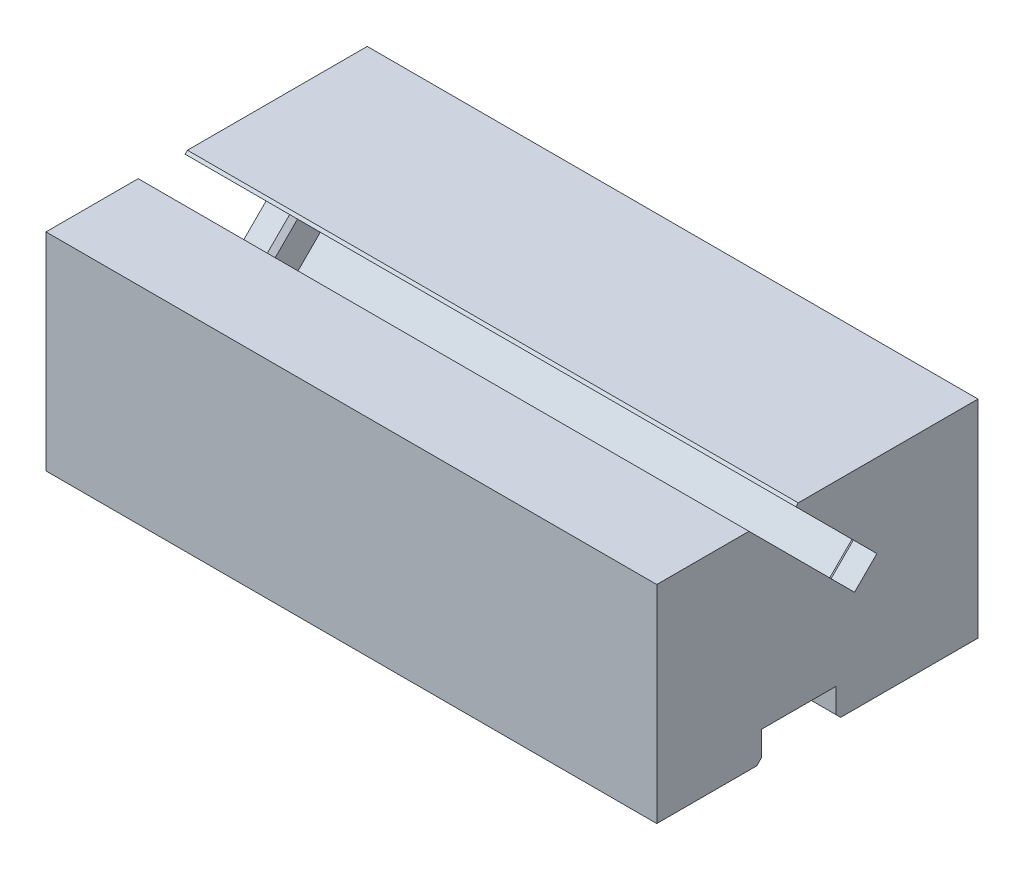
SolidWorks part; units mm, degrees
ref_plane "Front Plane" through (0, 0, 0) normal (0, 0, 1) x (1, 0, 0)
ref_plane "Top Plane" through (0, 0, 0) normal (0, 1, 0) x (1, 0, 0)
ref_plane "Right Plane" through (0, 0, 0) normal (1, 0, 0) x (0, 0, -1)
sketch "Sketch1" plane through (0, 0, 0) normal (1, 0, 0) x (0, 0, -1)
  line L0 (0, 0) -> (0, 19.2836)
  line L1 (0, 19.2836) -> (10, 19.2836)
  line L2 (34.8437, 19.2836) -> (34.8437, 0)
  line L3 (34.8437, 0) -> (0, 0)
  line L4 (10, 19.2836) -> (24.2836, 5)
  line L5 (24.2836, 5) -> (26.7054, 7.4218)
  line L6 (26.7054, 7.4218) -> (14.8437, 19.2836)
  line L7 (23.877, 10.2503) -> (21.4551, 7.8284)
  line L8 (14.8437, 19.2836) -> (34.8437, 19.2836)
  dimension "D2" = 20.2
  dimension "D3" = 3.425
  dimension "D4" = 10
  dimension "D5" = 20
  dimension "D6" = 5
  dimension "D7" = 4
  dimension "D1" = 45
extrude "Boss-Extrude1" add sketch "Sketch1" along normal blind 66.25 contours L8 L6 L5 L4 L1 L0 L3 L2 region at (0, 9.3206, -17.2678)
extrude "Boss-Extrude2" add sketch "Sketch1<4>" along normal blind 3.05 contours L6 L7 L4 L5 region at (0, 7.6251, -24.0803)
sketch "Sketch1<4>" plane through (0, 0, 0) normal (1, 0, 0) x (0, 0, -1) same geometry as "Sketch1"
ref_plane "Plane1" through (33.125, 0, 0) normal (-1, 0, 0) x (0, 0, 1)
mirror "Mirror1" about plane through (33.125, 0, 0) normal (-1, 0, 0) of "Boss-Extrude2"
sketch "Sketch2" plane through (0, 0, 0) normal (0, 1, 0) x (1, 0, 0)
  line L0 (0, 0) -> (0, 11.3468)
  line L1 (0, 0) -> (0, 10) construction
  line L2 (0, 11.3468) -> (3.05, 11.3468)
  line L3 (3.05, 11.3468) -> (3.05, 7.2468)
  line L4 (3.05, 7.2468) -> (63.2, 7.2468)
  line L5 (63.2, 7.2468) -> (63.2, 11.3468)
  line L6 (63.2, 11.3468) -> (66.25, 11.3468)
  line L7 (66.25, 0) -> (66.25, 10) construction
  line L8 (66.25, 11.3468) -> (66.25, 0)
  line L9 (66.25, 0) -> (0, 0)
  line L10 (0, 34.8437) -> (0, 19.4468)
  line L11 (0, 14.8437) -> (0, 34.8437) construction
  line L12 (0, 19.4468) -> (3.05, 19.4468)
  line L13 (3.05, 19.4468) -> (3.05, 27.5968)
  line L14 (3.05, 27.5968) -> (63.2, 27.5968)
  line L15 (63.2, 27.5968) -> (63.2, 19.4468)
  line L16 (63.2, 19.4468) -> (66.25, 19.4468)
  line L17 (66.25, 14.8437) -> (66.25, 34.8437) construction
  line L18 (66.25, 19.4468) -> (66.25, 34.8437)
  line L19 (66.25, 34.8437) -> (0, 34.8437)
  line L20 (33.125, 34.879) -> (33.125, 0.1414) construction
  line L21 (0, 17.4218) -> (66.1, 17.4218) construction
  line L23 (0, 34.8437) -> (0, 0) construction
  circle A0 centre (12.2, 14.2468) radius 1.5
  circle A1 centre (54.05, 14.2468) radius 1.5
  point P33 (33.125, 34.8437)
  point P38 (0, 17.4218)
  line M21 (0, 0) -> (0, 34.8437)
  line M22 (0, 34.8437) -> (66.25, 34.8437)
  line M23 (66.25, 34.8437) -> (66.25, 0)
  line M24 (66.25, 0) -> (0, 0)
  dimension "D9" = 3
  dimension "D1" = 3.05
  dimension "D2" = 8.1
  dimension "D3" = 4.1
  dimension "D4" = 8.15
  dimension "D5" = 3.05
  dimension "D7" = 12.2
  dimension "D8" = 7
extrude "Boss-Extrude3" add sketch "Sketch2" against normal blind 3.175 contours L5 L6 L2 L3 L4 M23 M24 M21 | L16 L15 L14 L13 L12 M21 M22 M23 region at (33.125, 0, -3.9043) region at (33.125, 0, -30.4979)
extrude "Cut-Extrude1" cut sketch "Sketch2<4>" along normal blind 3 contours A1 | A0 region at (12.2, 0, -14.2468) region at (54.05, 0, -14.2468)
sketch "Sketch2<4>" plane through (0, 0, 0) normal (0, 1, 0) x (1, 0, 0) same geometry as "Sketch2"
chamfer "Chamfer1" distance 1.5 angle 45 4 edges at (12.2, 3, -15.7468) (54.05, 3, -15.7468) (12.2, 0, -15.7468) (54.05, 0, -15.7468)
chamfer "Chamfer3" distance 2.675 angle 45 1 edges at (33.125, 0, -27.5968)
chamfer "Chamfer4" distance 0.5 angle 45 13 edges at (3.05, 9.0393, -22.6661) (63.2, 9.0393, -22.6661) (33.125, 19.2836, -14.8437) (3.05, -3.175, -23.5218) (1.525, -3.175, -19.4468) (63.2, -3.175, -23.5218) (64.725, -3.175, -19.4468) (1.525, -3.175, -11.3468) (3.05, -3.175, -9.2968) (33.125, -3.175, -7.2468) (63.2, -3.175, -9.2968) (64.725, -3.175, -11.3468) (33.125, -3.175, -27.5968) first distance on face at (1.525, 9.0393, -22.6661) first distance on face at (63.2, 7.6251, -24.0803) first distance on face at (33.125, 19.2836, -24.8437) first distance on face at (33.125, -3.175, -25.3336) first distance on face at (1.525, -1.5875, -11.3468) first distance on face at (3.05, -1.5875, -9.2968) first distance on face at (33.125, -1.5875, -7.2468) first distance on face at (63.2, -1.5875, -9.2968) first distance on face at (64.725, -1.5875, -11.3468)
equation "\"D2@Sketch1\"=20.05 + 0.15"
equation "\"D3@Sketch1\"=3.175 + 0.25"
equation "\"D5@Sketch2\"=\"D1@Sketch2\""
equation "\"D2@Sketch2\"=8.00 + 0.10"
equation "\"D4@Sketch2\"=8.05 + 0.10"
equation "\"D3@Sketch2\"=4.00 + 0.10"
